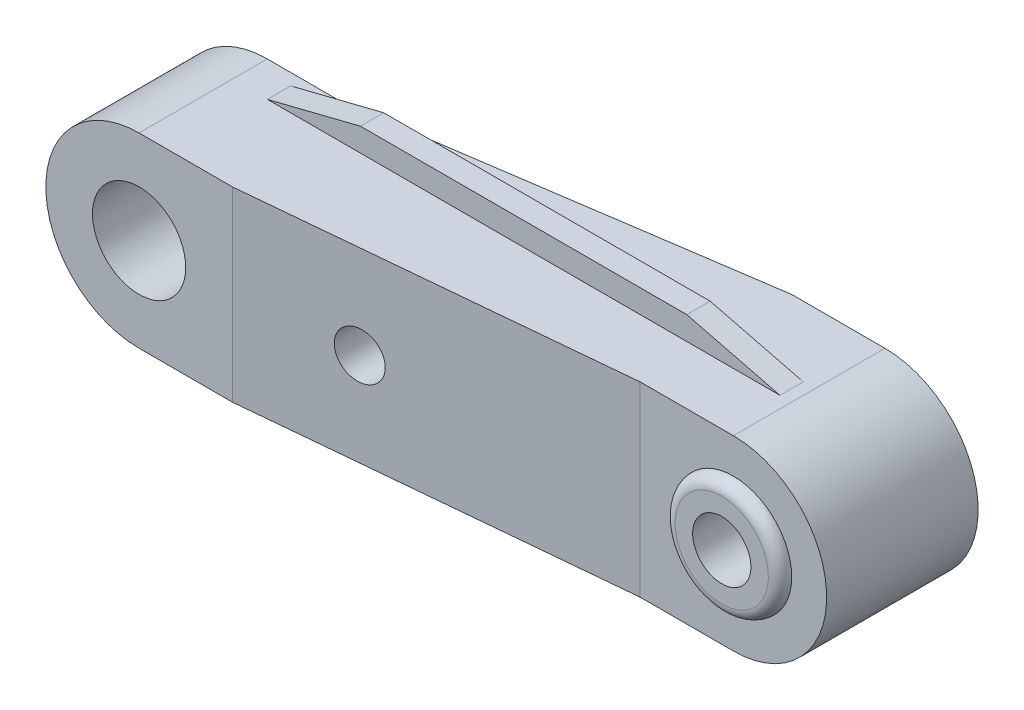
SolidWorks part; units mm, degrees
ref_plane "Plane1" through (0, 0, 0) normal (0, 0, 1) x (1, 0, 0)
ref_plane "Plane2" through (0, 0, 0) normal (0, 1, 0) x (1, 0, 0)
ref_plane "Plane3" through (0, 0, 0) normal (1, 0, 0) x (0, 0, -1)
sketch "Esquisse1" plane through (0, 0, 0) normal (0, 0, 1) x (1, 0, 0)
  line L0 (0, 4) -> (24, 4)
  line L1 (24, -4) -> (0, -4)
  line L2 (0, 0) -> (24, 0) construction
  arc A0 (0, 4) -> (0, -4) centre (0, 0) ccw
  arc A1 (24, -4) -> (24, 4) centre (24, 0) ccw
  dimension "D1" = 8
  dimension "D2" = 24
  dimension "D3" = 8
extrude "Base-Extrusion" add sketch "Esquisse1" along normal mid plane 9
sketch "Esquisse2" plane through (0, 0, 0) normal (0, 0, 1) x (1, 0, 0)
  line L0 (5.5, 5) -> (1.5, 4)
  line L2 (24, 4) -> (0, 4) construction
  line L3 (19.5, 5) -> (5.5, 5)
  line L4 (0, 0) -> (28, 0) construction
  line L5 (19.5, 5) -> (23.5, 4)
  line L6 (5.5, -5) -> (1.5, -4)
  line L7 (19.5, -5) -> (5.5, -5)
  line L8 (19.5, -5) -> (23.5, -4)
  line L9 (1.5, 4) -> (1.5, -4)
  line L10 (23.5, 4) -> (23.5, -4)
  point P7 (12.5, 5)
  dimension "D1" = 12.5
  dimension "D2" = 14
  dimension "D3" = 4
  dimension "D4" = 4
extrude "Boss.-Extru.1" add sketch "Esquisse2" along normal mid plane 1
sketch "Esquisse3" plane through (0, -4, 0) normal (0, -1, 0) x (1, 0, 0)
  line L0 (29, 3) -> (20, 3)
  line L3 (20, 3) -> (4.0136, 4.5)
  line L4 (24, 4.5) -> (0, 4.5) construction
  line L5 (4.0136, 4.5) -> (-6, 4.5)
  line L6 (29, 6) -> (29, 3)
  line L7 (29, 6) -> (-6, 6)
  line L8 (-6, 6) -> (-6, 4.5)
  line L9 (24, -4.5) -> (28, -4.5) construction
  dimension "D1" = 7.5
extrude "Enlèv. mat.-Extru.1" cut sketch "Esquisse3" against normal through all
sketch "Esquisse4" plane through (0, -4, 0) normal (0, -1, 0) x (1, 0, 0)
  line L0 (-6, -1) -> (3.1451, -1)
  line L1 (3.1451, -1) -> (20, -3.5)
  line L3 (20, -3.5) -> (29.2076, -3.5)
  line L4 (29.2076, -4.5) -> (29.2076, -7.5)
  line L5 (29.2076, -7.5) -> (-6, -7.5)
  line L6 (-6, -7.5) -> (-6, -1)
  line L7 (0, 4.5) -> (-4, 4.5) construction
  line L8 (29.2076, -3.5) -> (29.2076, -4.5)
  dimension "D1" = 5.5
  dimension "D2" = 3
  dimension "D3" = 2.5
extrude "Enlèv. mat.-Extru.2" cut sketch "Esquisse4" against normal through all
sketch "Esquisse5" plane through (0, 0, 4.5) normal (0, 0, 1) x (1, 0, 0)
  circle A0 centre (24, 0) radius 1.25
  circle A1 centre (9, 0) radius 1
  dimension "D1" = 2.5
  dimension "D2" = 2
  dimension "D3" = 15
extrude "Enlèv. mat.-Extru.3" cut sketch "Esquisse5" against normal through all
ref_plane "Plan1" through (0, 0, 0.5) normal (0, 0, -1) x (-1, 0, 0)
sketch "Esquisse11" plane through (0, 0, 3) normal (0, 0, 1) x (1, 0, 0)
  circle A0 centre (24, 0) radius 2.5
  dimension "D1" = 5
extrude "Boss.-Extru.2" add sketch "Esquisse11" along normal blind 0.5
fillet "Congé1" radius 0.5
sketch "Esquisse12" plane through (0, 0, 3.5) normal (0, 0, 1) x (1, 0, 0)
  circle A0 centre (24, 0) radius 1.25
  dimension "D1" = 2.5
extrude "Enlèv. mat.-Extru.5" cut sketch "Esquisse12" against normal through all
sketch "Esquisse13" plane through (0, 0, 4.5) normal (0, 0, 1) x (1, 0, 0)
  circle A0 centre (0, 0) radius 2
  dimension "D1" = 4
extrude "Enlèv. mat.-Extru.6" cut sketch "Esquisse13" against normal through all
sketch "Esquisse14" plane through (0, 0, -3.5) normal (0, 0, -1) x (-1, 0, 0)
  line L0 (0, 0) -> (-28, 0) construction
  line L1 (-2.8723, 2.5) -> (-6.1277, 2.5)
  line L2 (-2.8723, -2.5) -> (-6.1277, -2.5)
  line L3 (-11.8723, -2.5) -> (-21.1277, -2.5)
  line L4 (-11.8723, 2.5) -> (-21.1277, 2.5)
  arc A0 (-2.462, 1.7143) -> (-2.462, -1.7143) centre (0, 0) ccw
  arc A1 (-6.538, -1.7143) -> (-6.538, 1.7143) centre (-9, 0) ccw
  arc A2 (-21.538, -1.7143) -> (-21.538, 1.7143) centre (-24, 0) ccw
  arc A3 (-11.462, 1.7143) -> (-11.462, -1.7143) centre (-9, 0) ccw
  arc A4 (-11.462, -1.7143) -> (-11.8723, -2.5) centre (-11.8723, -2) cw
  arc A5 (-11.8723, 2.5) -> (-11.462, 1.7143) centre (-11.8723, 2) cw
  arc A6 (-21.1277, 2.5) -> (-21.538, 1.7143) centre (-21.1277, 2) ccw
  arc A7 (-21.1277, -2.5) -> (-21.538, -1.7143) centre (-21.1277, -2) cw
  arc A8 (-6.538, -1.7143) -> (-6.1277, -2.5) centre (-6.1277, -2) ccw
  arc A9 (-6.1277, 2.5) -> (-6.538, 1.7143) centre (-6.1277, 2) ccw
  arc A10 (-2.462, 1.7143) -> (-2.8723, 2.5) centre (-2.8723, 2) ccw
  arc A11 (-2.8723, -2.5) -> (-2.462, -1.7143) centre (-2.8723, -2) ccw
  point P15 (-10.6583, -2.5)
  point P18 (-10.6583, 2.5)
  dimension "D3" = 6
  dimension "D4" = 6
  dimension "D5" = 6
  dimension "D7" = 0.5
  dimension "D1" = 9
  dimension "D2" = 24
  dimension "D6" = 5
extrude "Enlèv. mat.-Extru.7" cut sketch "Esquisse14" against normal blind 2.5
